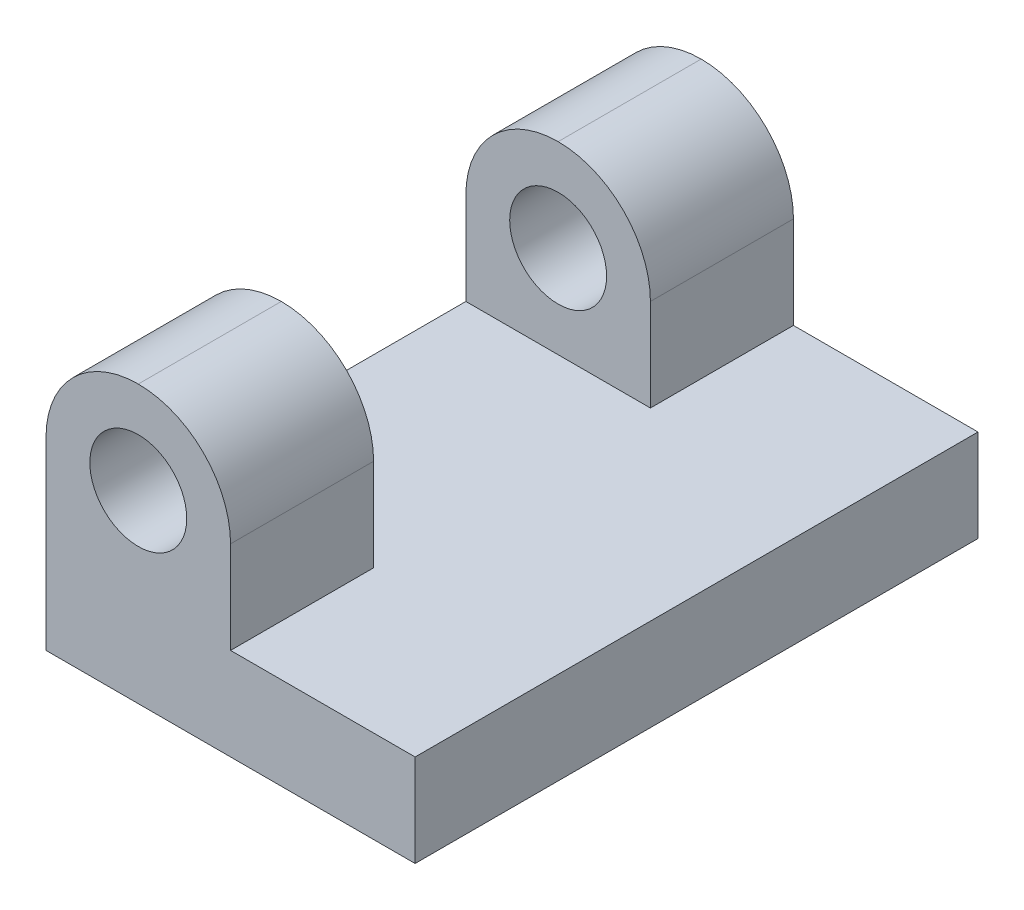
SolidWorks part; units mm, degrees
ref_plane "Front Plane" through (0, 0, 0) normal (0, 0, 1) x (1, 0, 0)
ref_plane "Top Plane" through (0, 0, 0) normal (0, 1, 0) x (1, 0, 0)
ref_plane "Right Plane" through (0, 0, 0) normal (1, 0, 0) x (0, 0, -1)
sketch "Sketch1" plane through (0, 0, 0) normal (0, 1, 0) x (1, 0, 0)
  line L1 (-6, -9.15) -> (6, -9.15)
  line L2 (-6, -9.15) -> (-6, 9.15)
  line L3 (-6, 9.15) -> (6, 9.15)
  line L4 (6, -9.15) -> (6, 9.15)
  line L5 (-6, -9.15) -> (6, 9.15) construction
  line L6 (-6, 9.15) -> (6, -9.15) construction
  point P0 (0, 0)
  dimension "D1" = 12
  dimension "D2" = 18.3
extrude "Boss-Extrude1" add sketch "Sketch1" along normal blind 3
sketch "Sketch2" plane through (0, 3, 0) normal (0, 1, 0) x (1, 0, 0)
  line L0 (-6, -9.15) -> (6, -9.15) construction
  line L1 (-6, 9.15) -> (0, 9.15)
  line L2 (-6, 9.15) -> (-6, -9.15)
  line L3 (-6, -9.15) -> (0, -9.15)
  line L4 (0, 9.15) -> (0, -9.15)
  dimension "D1" = 6
extrude "Boss-Extrude2" add sketch "Sketch2" along normal blind 6
sketch "Sketch3" plane through (0, 0, 9.15) normal (0, 0, 1) x (1, 0, 0)
  line L0 (-6, 9) -> (0, 9) construction
  line L1 (-6, 0) -> (6, 0) construction
  circle A0 centre (-3, 6) radius 1.575
  point P2 (0, 0)
  point P5 (-3, 9)
  dimension "D1" = 3.15
  dimension "D2" = 6
extrude "Cut-Extrude1" cut sketch "Sketch3" against normal through all
sketch "Sketch4" plane through (0, 9, 0) normal (0, 1, 0) x (1, 0, 0)
  line L0 (-6, 9.15) -> (-6, -9.15) construction
  line L1 (-6, 4.5) -> (0, 4.5)
  line L2 (-6, 4.5) -> (-6, -4.5)
  line L3 (-6, -4.5) -> (0, -4.5)
  line L4 (0, 4.5) -> (0, -4.5)
  line L5 (0, -9.15) -> (0, 9.15) construction
  line L6 (6, -9.15) -> (6, 9.15) construction
  point P10 (6, 0)
  point P11 (0, 0)
  dimension "D1" = 9
extrude "Cut-Extrude2" cut sketch "Sketch4" against normal up to surface (6 mm away) up to face at (3, 3, 0)
fillet "Fillet1" radius 3 4 edges at (-6, 9, 6.825) (0, 9, 6.825) (-6, 9, -6.825) (0, 9, -6.825)
